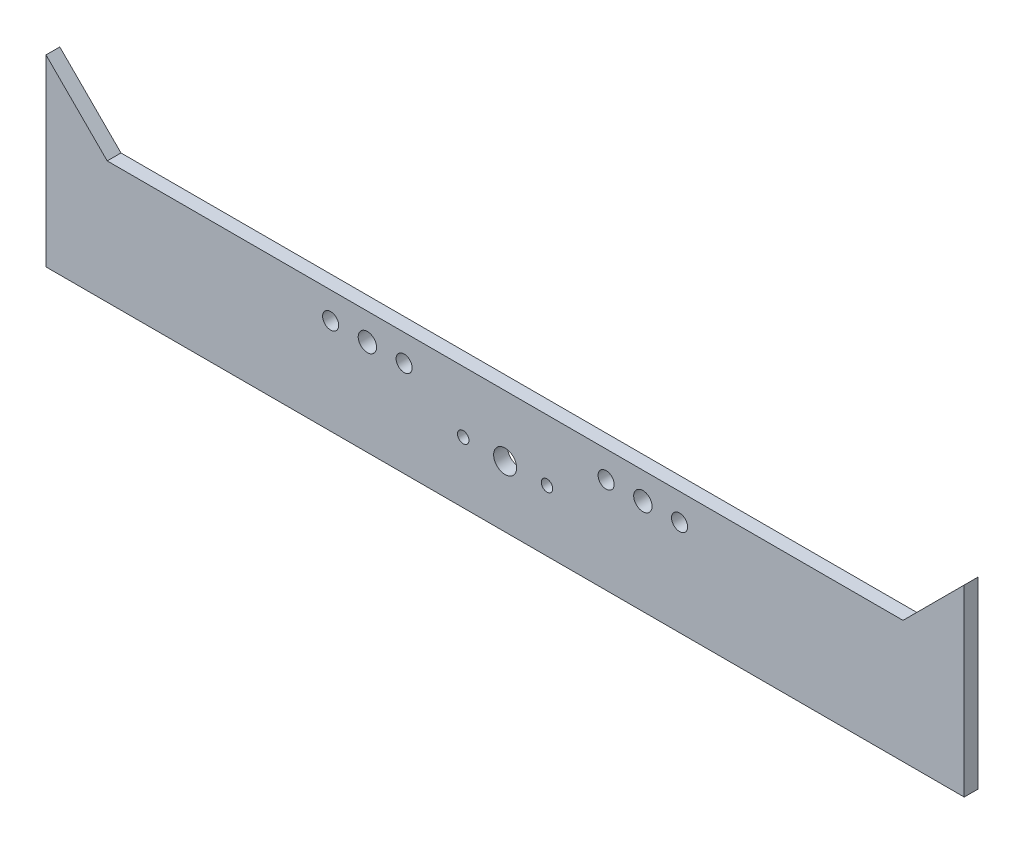
SolidWorks part; units mm, degrees
ref_plane "Front Plane" through (0, 0, 0) normal (0, 0, 1) x (1, 0, 0)
ref_plane "Top Plane" through (0, 0, 0) normal (0, 1, 0) x (1, 0, 0)
ref_plane "Right Plane" through (0, 0, 0) normal (1, 0, 0) x (0, 0, -1)
sketch "Sketch1" plane through (0, 0, 0) normal (0, 0, 1) x (1, 0, 0)
  line L0 (0, -1000) -> (0, 49000) construction
  line L1 (-1000, 0) -> (49000, 0) construction
  line L2 (-1173.1632, 53.3333) -> (48826.8368, 53.3333) construction
  line L3 (-200, 0) -> (200, 0)
  line L4 (-200, 0) -> (-200, 80)
  line L6 (200, 0) -> (200, 80)
  line L7 (200, 80) -> (173.3333, 53.3333)
  line L8 (-200, 80) -> (-173.3333, 53.3333)
  line L9 (-173.3333, 53.3333) -> (173.3333, 53.3333)
  dimension "D1" = 26.6667
  dimension "D2" = 400
  dimension "D3" = 80
  dimension "D5" = 45
extrude "Boss-Extrude1" add sketch "Sketch1" along normal blind 6
sketch "Sketch2" plane through (0, 0, 6) normal (0, 0, 1) x (1, 0, 0)
  line L0 (0, -1000) -> (0, 49000) construction
  line L1 (-1200, 26.665) -> (48800, 26.665) construction
  line L4 (-200, 0) -> (200, 0) construction
  line L5 (44, 41.665) -> (76, 41.665) construction
  circle A0 centre (0, 26.665) radius 5
  circle A5 centre (60, 41.665) radius 4
  circle A6 centre (76, 41.665) radius 3.5
  circle A7 centre (44, 41.665) radius 3.5
  circle A8 centre (-44, 41.665) radius 3.5
  circle A9 centre (-76, 41.665) radius 3.5
  circle A10 centre (-60, 41.665) radius 4
  circle A11 centre (18.25, 26.665) radius 2.5
  circle A12 centre (-18.25, 26.665) radius 2.5
  point P22 (60, 41.665)
  dimension "D1" = 10
  dimension "D8" = 8
  dimension "D10" = 7
  dimension "D11" = 7
  dimension "D3" = 5
  dimension "D2" = 26.665
  dimension "D4" = 18.25
  dimension "D6" = 15
  dimension "D7" = 60
  dimension "D9" = 32
extrude "Cut-Extrude1" cut sketch "Sketch2" against normal through all
